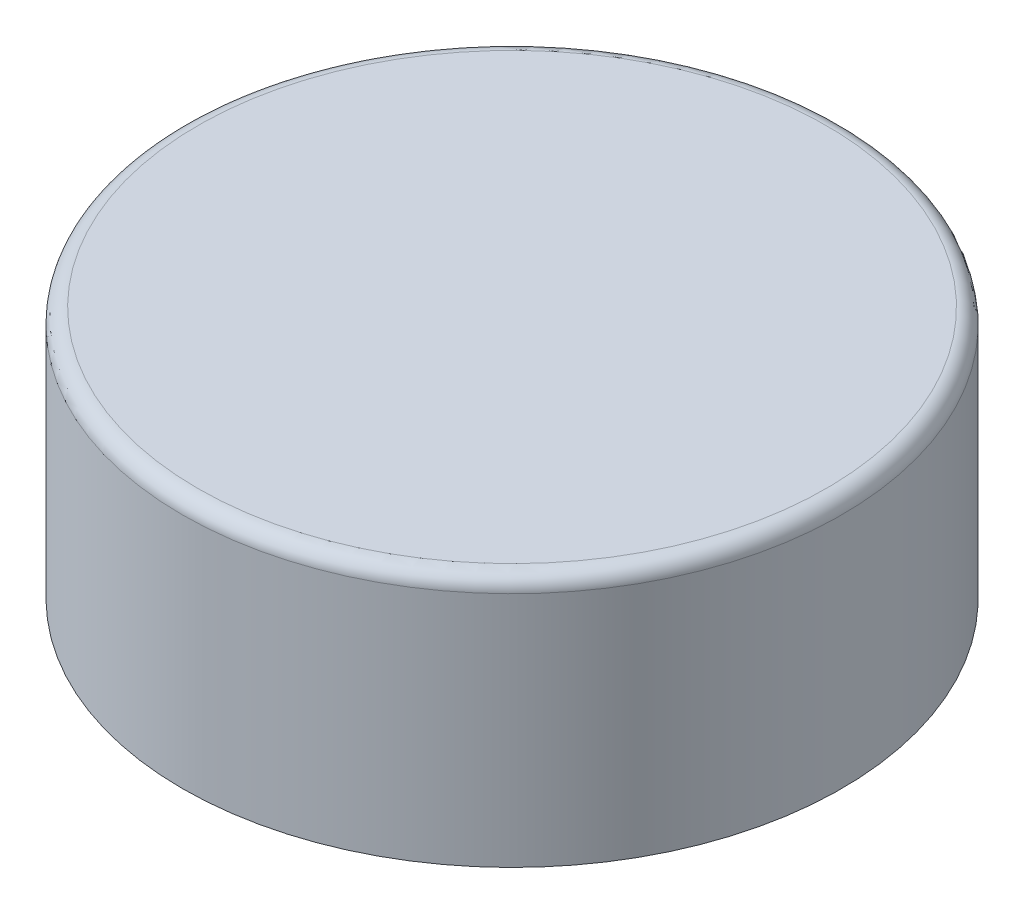
SolidWorks part; units mm, degrees
ref_plane "Front Plane" through (0, 0, 0) normal (0, 0, 1) x (1, 0, 0)
ref_plane "Top Plane" through (0, 0, 0) normal (0, 1, 0) x (1, 0, 0)
ref_plane "Right Plane" through (0, 0, 0) normal (1, 0, 0) x (0, 0, -1)
sketch "Sketch1" plane through (0, 0, 0) normal (0, 1, 0) x (1, 0, 0)
  circle A1 centre (0, 0) radius 40.1
  circle A2 centre (0, 0) radius 43.1
  dimension "D1" = 80.2
  dimension "D2" = 3
extrude "Boss-Extrude1" add sketch "Sketch1" against normal blind 33
extrude "Boss-Extrude2" add sketch "Sketch1<2>" against normal blind 3 contours A1 region at (0, 0, 0)
sketch "Sketch1<2>" plane through (0, 0, 0) normal (0, 1, 0) x (1, 0, 0) same geometry as "Sketch1"
fillet "Fillet1" radius 2 2 edges at (0, -3, 40.1) (0, 0, 43.1)
